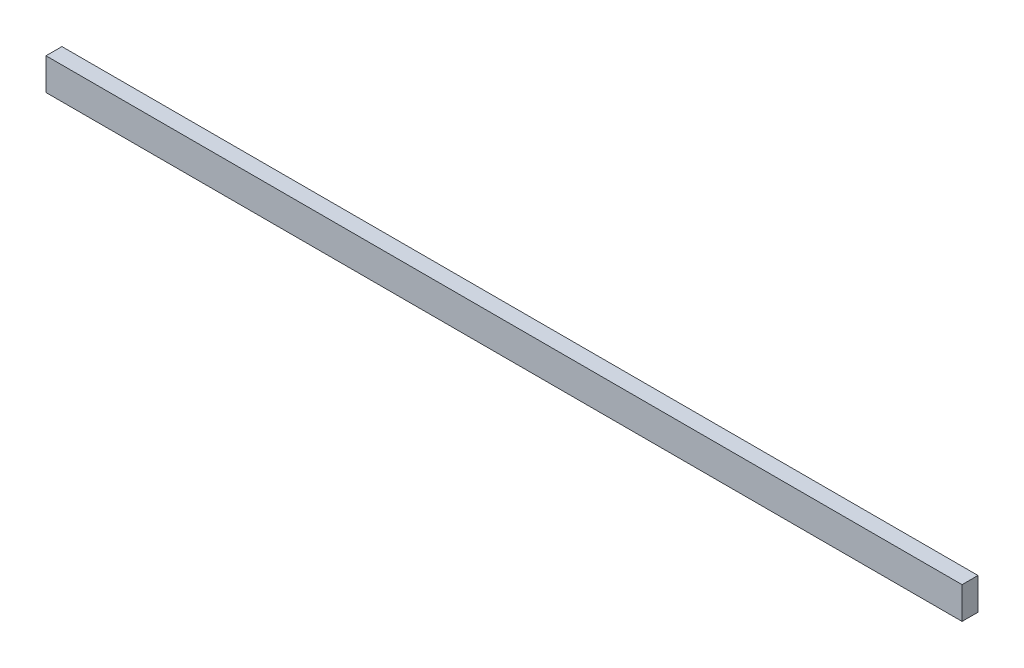
SolidWorks part; units mm, degrees
material "Pine"
ref_plane "Front Plane" through (0, 0, 0) normal (0, 0, 1) x (1, 0, 0)
ref_plane "Top Plane" through (0, 0, 0) normal (0, 1, 0) x (1, 0, 0)
ref_plane "Right Plane" through (0, 0, 0) normal (1, 0, 0) x (0, 0, -1)
sketch "Sketch1" plane through (0, 0, 0) normal (1, 0, 0) x (0, 0, -1)
  line L1 (0, 0) -> (40, 0)
  line L2 (0, 0) -> (0, -80)
  line L3 (0, -80) -> (40, -80)
  line L4 (40, 0) -> (40, -80)
  dimension "D1" = 80
  dimension "D2" = 40
extrude "Boss-Extrude1" add sketch "Sketch1" along normal blind 2300
